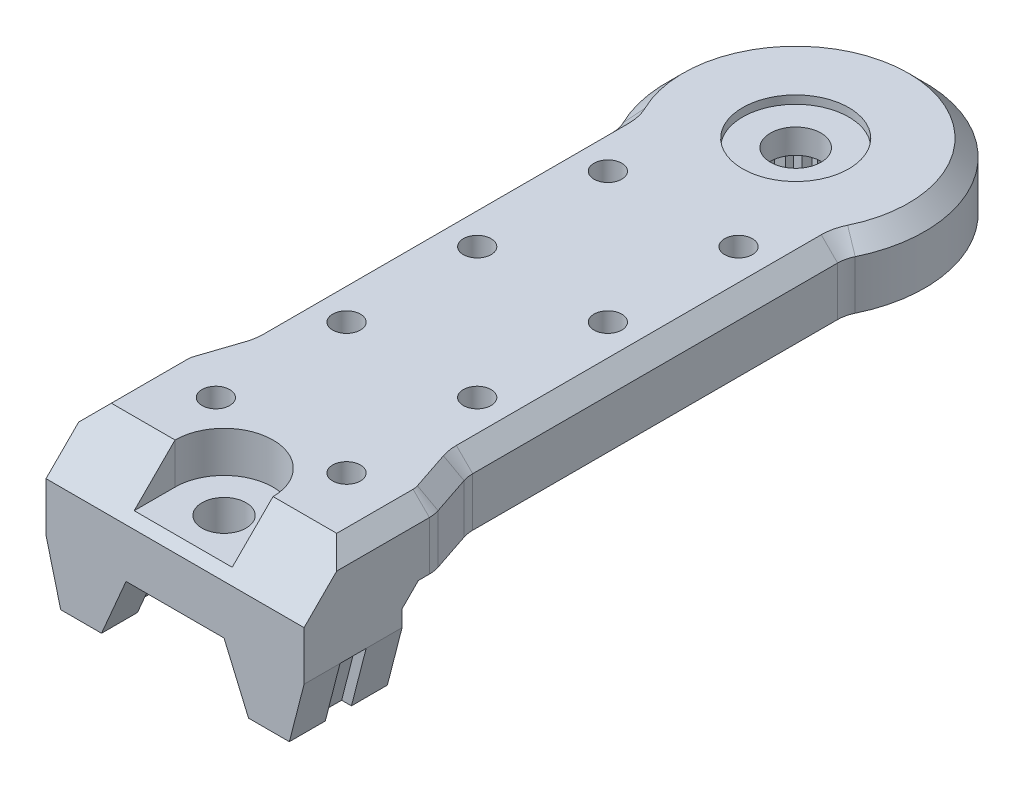
SolidWorks part; units mm, degrees
material "ABS"
ref_plane "正面" through (0, 0, 0) normal (0, 0, 1) x (1, 0, 0)
ref_plane "平面" through (0, 0, 0) normal (0, 1, 0) x (1, 0, 0)
ref_plane "右側面" through (0, 0, 0) normal (1, 0, 0) x (0, 0, -1)
sketch "ｽｹｯﾁ1" plane through (0, 0, 0) normal (0, 1, 0) x (1, 0, 0)
  line L2 (-7.9, 0) -> (-7.9, -38)
  line L3 (-7.9, -38) -> (7.9, -38)
  line L4 (7.9, 0) -> (7.9, -38)
  line L5 (-7.9, 0) -> (7.9, -38) construction
  line L6 (-7.9, -38) -> (7.9, 0) construction
  arc A0 (7.9, 0) -> (-7.9, 0) centre (0, 0) ccw
  point P7 (0, -19)
  dimension "D2" = 0
  dimension "D4" = 38
  dimension "D3" = 15.8
extrude "ﾎﾞｽ - 押し出し1" add sketch "ｽｹｯﾁ1" along normal blind 4
sketch "ｽｹｯﾁ4" plane through (0, 0, 38) normal (0, 0, 1) x (1, 0, 0)
  line L1 (-7, -5.5) -> (-4.5, -5.5)
  line L2 (-4.5, -5.5) -> (-3, -2)
  line L3 (-3, -2) -> (3, -2)
  line L4 (3, -2) -> (4.5, -5.5)
  line L5 (4.5, -5.5) -> (7, -5.5)
  line L7 (7.9, 0) -> (-7.9, 0)
  line L8 (7, -5.5) -> (7.9, -2)
  line L9 (7.9, -2) -> (7.9, 0)
  line L10 (-7, -5.5) -> (-7.9, -2)
  line L11 (-7.9, -2) -> (-7.9, 0)
  dimension "D1" = 5.5
  dimension "D2" = 3.5
  dimension "D3" = 3
  dimension "D4" = 7
  dimension "D5" = 2.5
  dimension "D9" = 2
  dimension "D10" = 2
extrude "ﾎﾞｽ - 押し出し3" add sketch "ｽｹｯﾁ4" against normal blind 6
chamfer "面取り1" distance 3 angle 45 1 edges at (0, 4, 38)
sketch "ｽｹｯﾁ5" plane through (0, 4, 0) normal (0, 1, 0) x (1, 0, 0)
  line L0 (-4, -31.5) -> (4, -31.5) construction
  line L1 (7.9, -38) -> (-7.9, -38) construction
  circle A0 centre (-4, -31.5) radius 0.85
  circle A1 centre (4, -31.5) radius 0.85
  dimension "D1" = 1.7
  dimension "D2" = 1.7
  dimension "D4" = 4
  dimension "D3" = 8
  dimension "D5" = 6.5
extrude "ｶｯﾄ - 押し出し1" cut sketch "ｽｹｯﾁ5" against normal blind 4
pattern_linear "直線ﾊﾟﾀｰﾝ1" count 4 spacing 8 along (0, 0, -1) of "ｶｯﾄ - 押し出し1"
sketch "ｽｹｯﾁ6" plane through (0, 4, 0) normal (0, 1, 0) x (1, 0, 0)
  line L0 (-3, -35) -> (-3, -39)
  line L1 (-3, -39) -> (3, -39)
  line L2 (3, -39) -> (3, -35)
  line L3 (7.9, -38) -> (-7.9, -38) construction
  arc A0 (3, -35) -> (-3, -35) centre (0, -35) ccw
  dimension "D1" = 6
  dimension "D3" = 3
  dimension "D2" = 0
  dimension "D4" = 4
extrude "ｶｯﾄ - 押し出し2" cut sketch "ｽｹｯﾁ6" against normal blind 2.5
sketch "ｽｹｯﾁ7" plane through (0, 1.5, 0) normal (0, 1, 0) x (1, 0, 0)
  circle A0 centre (0, -35) radius 1.35
  dimension "D1" = 2.7
extrude "ｶｯﾄ - 押し出し3" cut sketch "ｽｹｯﾁ7" against normal up to next
sketch "ｽｹｯﾁ8" plane through (0, 0, 0) normal (0, -1, 0) x (1, 0, 0)
  circle A0 centre (0, 0) radius 3.95
  dimension "D1" = 7.9
extrude "ﾎﾞｽ - 押し出し4" add sketch "ｽｹｯﾁ8" along normal blind 1.2
sketch "ｽｹｯﾁ9" plane through (0, 4, 0) normal (0, 1, 0) x (1, 0, 0)
  circle A0 centre (0, 0) radius 3.25
  dimension "D1" = 6.5
extrude "ｶｯﾄ - 押し出し4" cut sketch "ｽｹｯﾁ9" against normal blind 0.5
sketch "ｽｹｯﾁ10" plane through (0, 4, 0) normal (0, 1, 0) x (1, 0, 0)
  circle A0 centre (0, 0) radius 1.55
  dimension "D1" = 3.1
extrude "ｶｯﾄ - 押し出し5" cut sketch "ｽｹｯﾁ10" against normal through all
fillet "ﾌｨﾚｯﾄ1" radius 0.5 1 edges at (0, 0, 3.95)
sketch "ｽｹｯﾁ11" plane through (0, -1.2, 0) normal (0, -1, 0) x (1, 0, 0)
  circle A0 centre (0, 0) radius 3
  dimension "D1" = 6
extrude "ｶｯﾄ - 押し出し6" cut sketch "ｽｹｯﾁ11" against normal blind 3.2
sketch "ｽｹｯﾁ12" plane through (0, -1.2, 0) normal (0, -1, 0) x (1, 0, 0)
  line L0 (0, 0) -> (-0.4085, 2.9721) construction
  line L1 (-0.4085, 2.9721) -> (0, 2.5745)
  line L2 (0, 2.5745) -> (0.4085, 2.9721)
  line L3 (0.4085, 2.9721) -> (0, 0) construction
  line L4 (0, 2.5745) -> (0, 0) construction
  circle A0 centre (0, 0) radius 3 construction
  circle A1 centre (0, 0) radius 3 construction
  arc A2 (-0.4085, 2.9721) -> (0.4085, 2.9721) centre (0, 0) cw
  dimension "D1" = 15.652
  dimension "D2" = 0.57
extrude "ﾎﾞｽ - 押し出し5" add sketch "ｽｹｯﾁ12" against normal up to next
pattern_circular "円形ﾊﾟﾀｰﾝ1" count 23 over 360 about axis through (0, 2, 0) along (0, -1, 0) of "ﾎﾞｽ - 押し出し5"
ref_plane "平面1" through (0, 0, 35) normal (0, 0, 1) x (1, 0, 0)
sketch "ｽｹｯﾁ13" plane through (0, 0, 35) normal (0, 0, 1) x (1, 0, 0)
  line L0 (3, -2) -> (4.5, -5.5)
  line L1 (3, -2) -> (3.6, -2)
  line L2 (4.5, -5.5) -> (5.1, -5.5)
  line L3 (3.6, -2) -> (5.1, -5.5)
  line L4 (3, -2) -> (5.1, -5.5) construction
  line L5 (4.5, -5.5) -> (3.6, -2) construction
  line L6 (4.5, -5.5) -> (7, -5.5) construction
  line L7 (6.4, -5.5) -> (7, -5.5)
  line L8 (6.4, -5.5) -> (7.3, -2)
  line L9 (7, -5.5) -> (7.9, -2)
  line L10 (7.3, -2) -> (7.9, -2)
  line L11 (6.4, -5.5) -> (7.9, -2) construction
  line L12 (7, -5.5) -> (7.3, -2) construction
  point P5 (4.05, -3.75)
  point P14 (7.15, -3.75)
  dimension "D1" = 0.6
extrude "ｶｯﾄ - 押し出し7" cut sketch "ｽｹｯﾁ13" against normal mid plane 1.6
mirror "ﾐﾗｰ1" about plane through (0, 0, 0) normal (1, 0, 0) of "ｶｯﾄ - 押し出し7"
sketch "ｽｹｯﾁ14" plane through (0, 4, 0) normal (0, 1, 0) x (1, 0, 0)
  line L0 (-7.9, 0) -> (-7.9, -30)
  line L1 (-7.9, 0) -> (-7.9, -35) construction
  line L2 (-7.9, -30) -> (-6.9, -27)
  line L3 (-6.9, -27) -> (-6.9, -3.8471)
  line L4 (7.9, -38) -> (-7.9, -38) construction
  arc A0 (-7.9, 0) -> (-6.9, -3.8471) centre (0, 0) ccw
  arc A1 (7.9, 0) -> (-7.9, 0) centre (0, 0) ccw construction
  dimension "D1" = 6.9
  dimension "D2" = 11
  dimension "D3" = 3
extrude "ｶｯﾄ - 押し出し8" cut sketch "ｽｹｯﾁ14" against normal through all
mirror "ﾐﾗｰ2" about plane through (0, 0, 0) normal (1, 0, 0) of "ｶｯﾄ - 押し出し8"
fillet "ﾌｨﾚｯﾄ2" radius 2 6 edges at (7.9, 2, 30) (6.9, 2, 27) (6.9, 2, 3.8471) (-6.9, 2, 3.8471) (-6.9, 2, 27) (-7.9, 2, 30)
chamfer "面取り2" distance 1 angle 45 16 edges at (-7.9, 4, 32.6623) (0, 4, -7.9) (7.9, 4, 32.6623) (6.2937, 0, 32) (-6.2937, 0, 32) (-7.8742, 4, 30.0042) (-7.4, 4, 28.5) (-6.9258, 4, 26.9958) (-6.9, 4, 15.5057) (-6.9512, 4, 3.8864) (6.9512, 4, 3.8864) (6.9, 4, 15.5057) (6.9258, 4, 26.9958) (7.4, 4, 28.5) (7.8742, 4, 30.0042) (0, 0, 32)
ref_axis "軸1" through (0, 3, 0) along (0, -1, 0)
